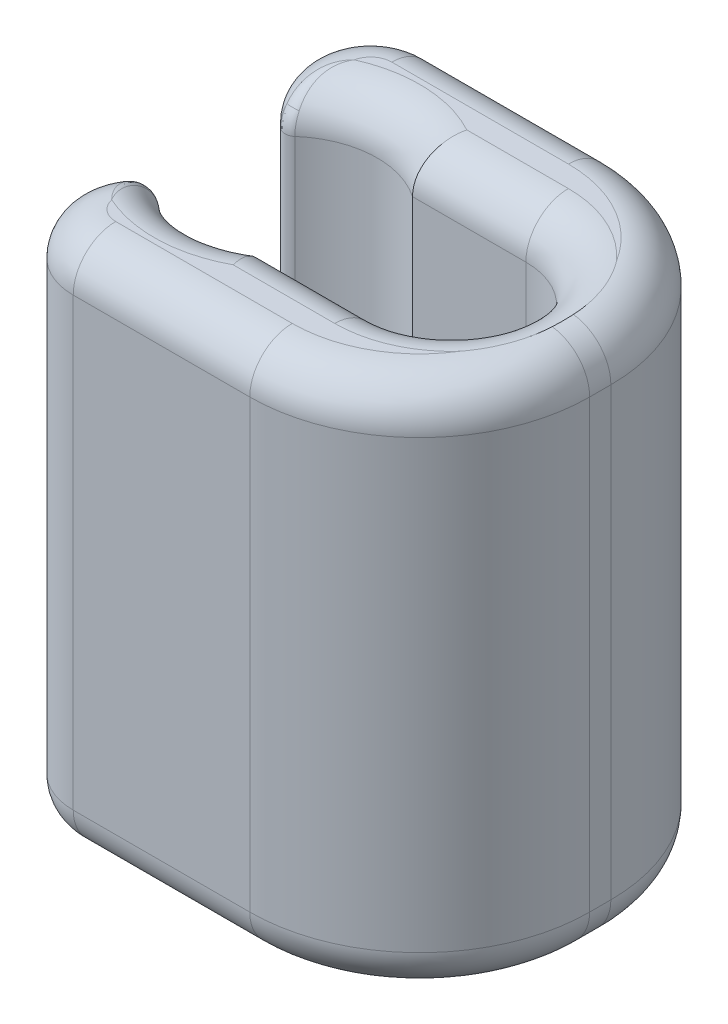
SolidWorks part; units mm, degrees
ref_plane "Alzado" through (0, 0, 0) normal (0, 0, 1) x (1, 0, 0)
ref_plane "Planta" through (0, 0, 0) normal (0, 1, 0) x (1, 0, 0)
ref_plane "Vista lateral" through (0, 0, 0) normal (1, 0, 0) x (0, 0, -1)
sketch "Croquis1" plane through (0, 0, 0) normal (0, 1, 0) x (1, 0, 0)
  line L0 (0, 0) -> (-9.2761, 8.5)
  line L1 (-9.2761, 8.5) -> (14.75, 8.5)
  line L2 (14.75, 8.5) -> (14.75, -8.5)
  line L3 (14.75, -8.5) -> (-9.2761, -8.5)
  line L4 (-9.2761, -8.5) -> (0, 0)
  line L5 (14.75, 0) -> (-18.2606, 0) construction
  line L6 (-9.2761, 8.5) -> (-9.2761, -8.5) construction
  line L7 (7.75, 3.5) -> (2.4109, 3.5)
  line L8 (7.75, -3.5) -> (2.4109, -3.5)
  circle A1 centre (0, 0) radius 4.25
  arc A4 (7.75, -3.5) -> (7.75, 3.5) centre (7.75, 0) ccw
  dimension "D2" = 7.75
  dimension "D3" = 7
  dimension "D6" = 8.5
  dimension "D1" = 85
  dimension "D4" = 17
  dimension "D5" = 7
extrude "Saliente-Extruir1" add sketch "Croquis1" along normal blind 25
fillet "Redondeo1" radius 3 2 edges at (-9.2761, 12.5, -8.5) (-9.2761, 12.5, 8.5)
fillet "Redondeo2" radius 8 2 edges at (14.75, 12.5, -8.5) (14.75, 12.5, 8.5)
fillet "Redondeo3" radius 2 24 edges at (-4.3577, 0, -6.5873) (-0.4789, 0, -4.2229) (5.0805, 0, -3.5) (11.25, 0, 0) (5.0805, 0, 3.5) (-0.4789, 0, 4.2229) (-4.3577, 0, 6.5873) (2.5942, 0, 8.5) (12.4069, 0, 6.1569) (14.75, 0, 0) (12.4069, 0, -6.1569) (2.5942, 0, -8.5) (12.4069, 25, 6.1569) (2.5942, 25, 8.5) (-4.3577, 25, 6.5873) (-0.4789, 25, 4.2229) (5.0805, 25, 3.5) (11.25, 25, 0) (5.0805, 25, -3.5) (-0.4789, 25, -4.2229) (-4.3577, 25, -6.5873) (2.5942, 25, -8.5) (12.4069, 25, -6.1569) (14.75, 25, 0)
fillet "Redondeo4" radius 0.5 10 edges at (-3.0864, 24.79, -4.3795) (-3.0864, 0.21, -4.3795) (-3.1334, 12.5, -2.8713) (-3.0864, 0.21, 4.3795) (-3.1334, 12.5, 2.8713) (-3.0864, 24.79, 4.3795) (-3.1374, 1.4675, -2.9729) (-3.1374, 1.4675, 2.9729) (-3.1374, 23.5325, -2.9729) (-3.1374, 23.5325, 2.9729)
